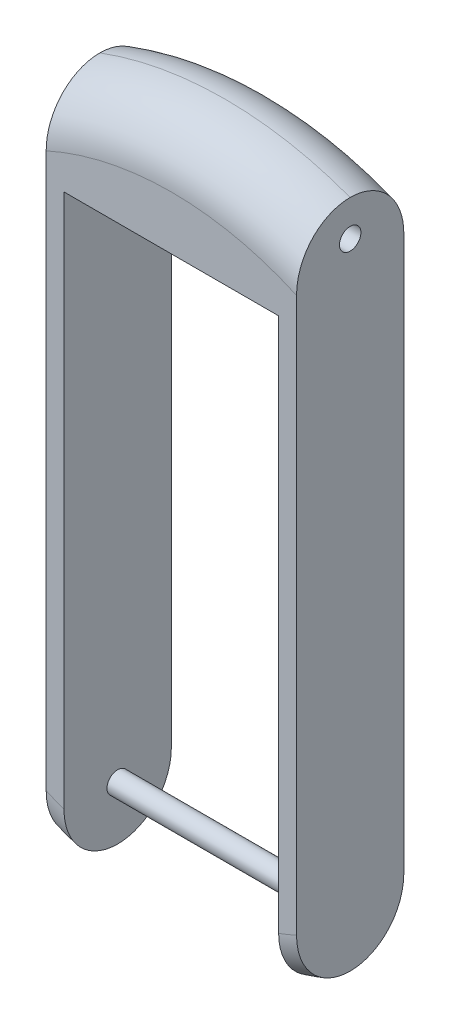
SolidWorks part; units mm, degrees
ref_plane "前视基准面" through (0, 0, 0) normal (0, 0, 1) x (1, 0, 0)
ref_plane "上视基准面" through (0, 0, 0) normal (0, 1, 0) x (1, 0, 0)
ref_plane "右视基准面" through (0, 0, 0) normal (1, 0, 0) x (0, 0, -1)
sketch "草图1" plane through (0, 0, 0) normal (0, 0, 1) x (1, 0, 0)
  line L0 (0, 100) -> (0, -100) construction
  line L2 (35, -93.675) -> (35, 93.675)
  line L4 (-35, 93.675) -> (-35, -93.675)
  arc A0 (-35, -93.675) -> (35, -93.675) centre (0, 0) ccw
  arc A1 (35, 93.675) -> (-35, 93.675) centre (0, 0) ccw
  dimension "D1" = 200
extrude "凸台-拉伸1" add sketch "草图1" along normal blind 30
sketch "草图2" plane through (35, 0, 0) normal (1, 0, 0) x (0, 0, -1)
  line L0 (0, 93.675) -> (0, 83.675) construction
  line L1 (0, -93.675) -> (0, 93.675) construction
  line L2 (0, 83.675) -> (-15, 83.675) construction
  circle A0 centre (-15, 83.675) radius 3
  dimension "D3" = 6
  dimension "D1" = 10
  dimension "D2" = 15
extrude "切除-拉伸1" cut sketch "草图2" against normal blind 192
fillet "圆角1" radius 15 1 edges at (0, 100, 0) type face fillet first side face at (0, 96.8375, 15) second side face at (0, 0, 0)
sketch "草图3" plane through (0, 0, 30) normal (0, 0, 1) x (1, 0, 0)
  line L0 (0, 100) -> (0, -100) construction
  line L1 (0, -100) -> (-30, -100)
  line L2 (-30, -100) -> (-30, 70)
  line L3 (-30, 70) -> (30, 70)
  line L4 (30, 70) -> (30, -100)
  line L5 (30, -100) -> (0, -100)
  arc A0 (35, 93.675) -> (-35, 93.675) centre (0, 0) ccw construction
  arc A1 (-35, -93.675) -> (35, -93.675) centre (0, 0) ccw construction
  dimension "D1" = 30
  dimension "D2" = 170
  dimension "D3" = 60
extrude "切除-拉伸2" cut sketch "草图3" against normal blind 192
sketch "草图4" plane through (35, 0, 0) normal (1, 0, 0) x (0, 0, -1)
  line L0 (0, -95.3939) -> (0, -80.3939) construction
  line L1 (0, -93.675) -> (0, 77.4597) construction
  line L2 (0, -80.3939) -> (-15, -80.3939) construction
  circle A0 centre (-15, -80.3939) radius 3
  dimension "D3" = 6
  dimension "D1" = 15
  dimension "D2" = 15
extrude "凸台-拉伸2" add sketch "草图4" against normal blind 66
fillet "圆角2" radius 15 1 edges at (0, 100, 30) type face fillet first side face at (0, -5.5661, 30) second side face at (0, 96.8375, 22.5)
fillet "圆角3" radius 15 1 edges at (32.5114, -94.5675, 30) type face fillet first side face at (0, -9.468, 30) second side face at (32.5057, -94.551, 15)
fillet "圆角4" radius 15 1 edges at (32.5114, -94.5675, 0) type face fillet first side face at (0, -9.468, 0) second side face at (32.5057, -94.551, 7.5)
fillet "圆角5" radius 15 1 edges at (-32.5114, -94.5675, 30) type face fillet first side face at (0.0006, -5.459, 30) second side face at (-32.5057, -94.551, 15)
fillet "圆角8" radius 15 1 edges at (-32.5114, -94.5675, 0) type face fillet first side face at (0.0006, -5.459, 0) second side face at (-32.5057, -94.551, 7.5)
